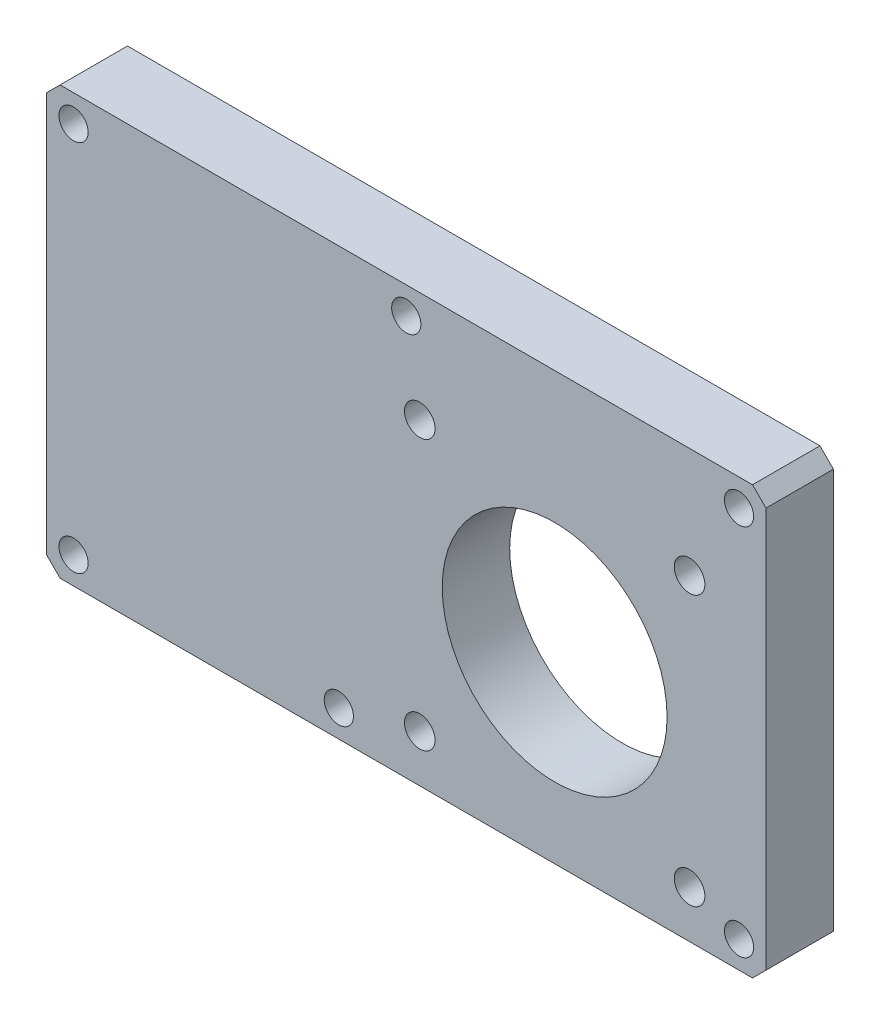
SolidWorks part; units mm, degrees
ref_plane "前视基准面" through (0, 0, 0) normal (0, 0, 1) x (1, 0, 0)
ref_plane "上视基准面" through (0, 0, 0) normal (0, 1, 0) x (1, 0, 0)
ref_plane "右视基准面" through (0, 0, 0) normal (1, 0, 0) x (0, 0, -1)
other "Configuration Table"
sketch "草图1" plane through (0, 0, 0) normal (0, 0, 1) x (1, 0, 0)
  line L1 (0, 0) -> (160, 0)
  line L2 (0, 0) -> (0, -95)
  line L3 (0, -95) -> (160, -95)
  line L4 (160, 0) -> (160, -95)
  dimension "D1" = 160
  dimension "D2" = 95
extrude "凸台-拉伸1" add sketch "草图1" along normal blind 15
chamfer "倒角1" distance 3 angle 45 4 edges at (160, -95, 7.5) (160, 0, 7.5) (0, -95, 7.5) (0, 0, 7.5)
sketch "草图2" plane through (0, 0, 0) normal (0, 0, -1) x (-1, 0, 0)
  circle A0 centre (-113, -54.25) radius 25
  dimension "D1" = 50
extrude "切除-拉伸1" cut sketch "草图2" against normal through all
hole_wizard "M8 螺纹孔1" positions "草图5" profile "草图4" tap size "M8" standard "GB"
sketch "草图5" plane through (0, 0, 0) normal (0, 0, -1) x (-1, 0, 0)
  point P0 (-143, -24.5)
  point P3 (-83, -24.5)
  point P6 (-83, -84.5)
  point P9 (-143, -84.5)
cosmetic thread "孔螺蚊线1" parameters "D1"=15, "D2"=8
cosmetic thread "孔螺蚊线2" parameters "D1"=15, "D2"=8
cosmetic thread "孔螺蚊线3" parameters "D1"=15, "D2"=8
cosmetic thread "孔螺蚊线4" parameters "D1"=15, "D2"=8
sketch "草图4" plane through (143, -24.5, 0) normal (1, 0, 0) x (0, 1, 0)
  line L0 (0, 0) -> (0, 22.0429)
  line L1 (0, 22.0429) -> (3.4, 20)
  line L2 (3.4, 20) -> (3.4, 0)
  line L5 (3.4, 0) -> (0, 0)
  line L10 (0, 22.0429) -> (-3.4, 20) construction
  line L11 (0, -6.35) -> (0, 107.95) construction
  dimension "螺纹孔钻头直径" = 6.8
  dimension "螺纹孔钻头深度" = 20
  dimension "导头角度" = 118
sketch "草图6" plane through (0, 0, 0) normal (0, 0, -1) x (-1, 0, 0)
  line L0 (-160, -92) -> (-160, -3) construction
  line L1 (-157, 0) -> (-3, 0) construction
  line L2 (-3, -95) -> (-157, -95) construction
  line L3 (0, -3) -> (0, -92) construction
  circle A0 centre (-154, -6) radius 5.25
  circle A1 centre (-80, -6) radius 5.25
  circle A2 centre (-6, -6) radius 5.25
  circle A4 centre (-6, -89) radius 5.25
  circle A5 centre (-154, -89) radius 5.25
  circle A6 centre (-65, -89) radius 5.25
  circle A7 centre (-80, -89) radius 5.25 [skipped]
  dimension "D1" = 10.5
  dimension "D6" = 10.5
  dimension "D2" = 6
  dimension "D3" = 6
  dimension "D7" = 6
  dimension "D8" = 65
  dimension "D4" = 3
  dimension "D5" = 2
extrude "切除-拉伸2" cut sketch "草图6" against normal blind 7
sketch "草图7" plane through (0, 0, 7) normal (0, 0, -1) x (-1, 0, 0)
  circle A0 centre (-154, -6) radius 5.25 construction
  circle A1 centre (-154, -6) radius 5.25 construction
  circle A2 centre (-154, -6) radius 3.25
  circle A3 centre (-80, -6) radius 3.25
  circle A4 centre (-6, -6) radius 3.25
  circle A6 centre (-6, -89) radius 3.25
  circle A7 centre (-154, -89) radius 3.25
  circle A8 centre (-65, -89) radius 3.25
  circle A9 centre (-65, -89) radius 5.25
  circle A10 centre (-65, -89) radius 5.25 construction
  circle A11 centre (-80, -89) radius 3.25 [skipped]
  dimension "D1" = 6.5
  dimension "D5" = 6.5
  dimension "D4" = 0
  dimension "D2" = 3
  dimension "D3" = 2
extrude "切除-拉伸3" cut sketch "草图7" against normal through all
